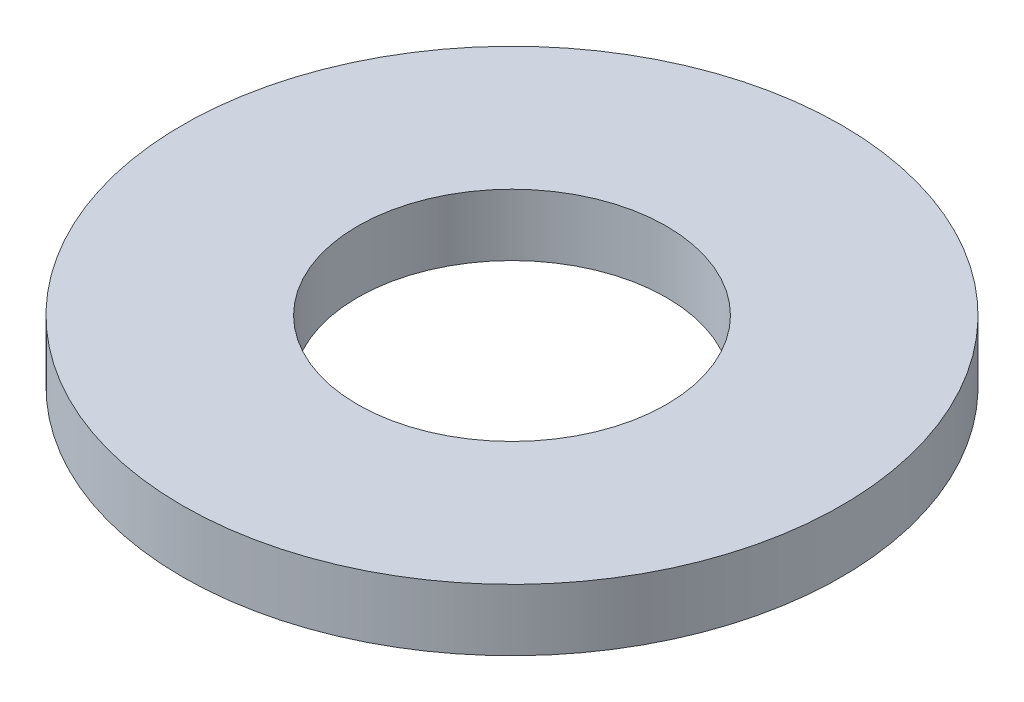
SolidWorks part; units mm, degrees
ref_plane "Front Plane" through (0, 0, 0) normal (0, 0, 1) x (1, 0, 0)
ref_plane "Top Plane" through (0, 0, 0) normal (0, 1, 0) x (1, 0, 0)
ref_plane "Right Plane" through (0, 0, 0) normal (1, 0, 0) x (0, 0, -1)
sketch "Sketch1" plane through (0, 0, 0) normal (0, 1, 0) x (1, 0, 0)
  circle A0 centre (0, 0) radius 80
  dimension "FLANGE_OD" = 160
extrude "Boss-Extrude1" add sketch "Sketch1" along normal blind 15
sketch "Sketch2" plane through (0, 0, 0) normal (0, 1, 0) x (1, 0, 0)
  circle A0 centre (0, 0) radius 37.5
  dimension "BORE_D" = 75
extrude "Cut-Extrude1" cut sketch "Sketch2" along normal through all
sketch "Sketch3" plane through (0, 15, 0) normal (0, 1, 0) x (1, 0, 0)
  circle A0 centre (0, 0) radius 27.1133 construction
  circle A1 centre (-27.1133, 0) radius 6.8406
  dimension "BOLT_D" = 13.6813
  dimension "BOLT_PCD" = 54.2265
extrude "Cut-Extrude2" cut sketch "Sketch3" against normal blind 11.9485 rebuild error yes
pattern_circular "CirPattern1" count 3 over 360 rebuild error yes
